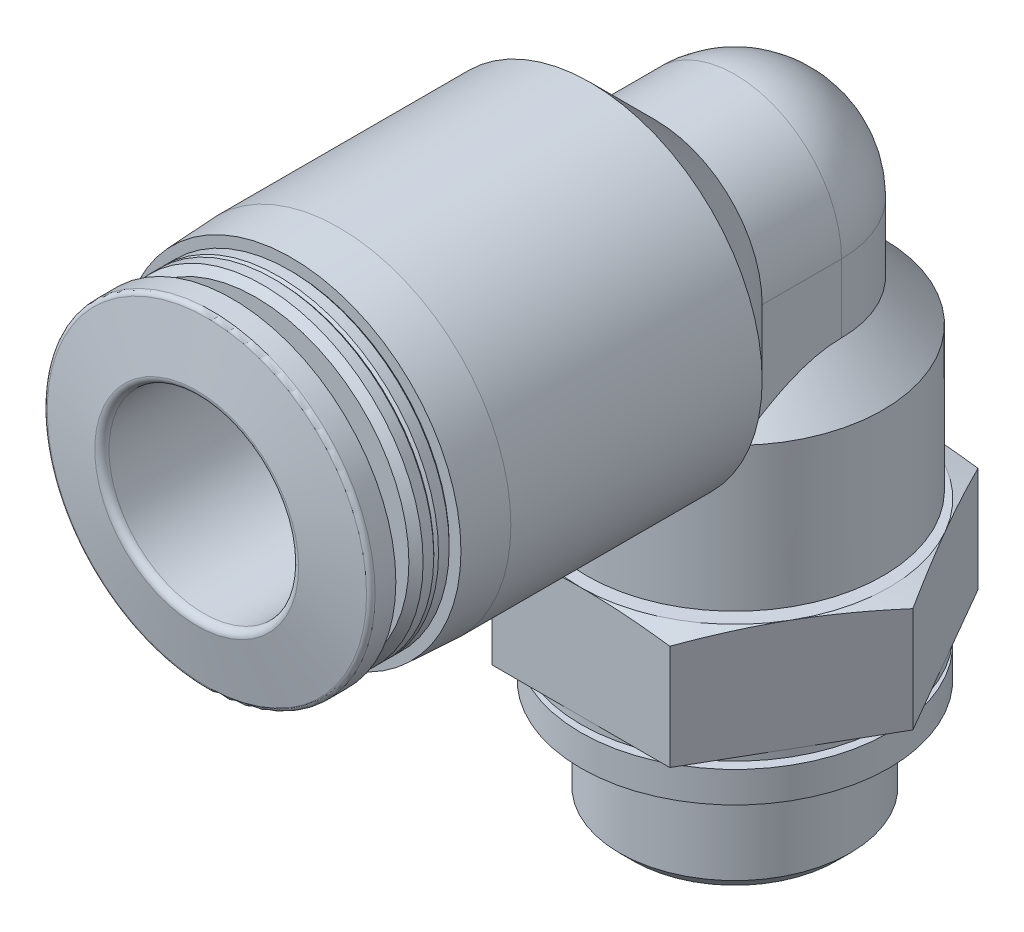
SolidWorks part; units mm, degrees
note: '?' marks a value the reader was unsure of.
ref_plane "Ebene vorne" through (0, 0, 0) normal (0, 0, 1) x (1, 0, 0)
ref_plane "Ebene oben" through (0, 0, 0) normal (0, 1, 0) x (1, 0, 0)
ref_plane "Ebene rechts" through (0, 0, 0) normal (1, 0, 0) x (0, 0, -1)
sketch "Skizze1" plane through (0, 0, 0) normal (0, 0, 1) x (1, 0, 0)
  line L0 (4.495, 17.9) -> (4.495, 15.015)
  line L1 (4.495, 15.015) -> (6.25, 13.26)
  line L2 (6.25, 13.26) -> (6.25, 7.2)
  line L3 (6.25, 7.2) -> (5.625, 6.9)
  line L4 (5.625, 6.9) -> (6.5, 6.9)
  line L5 (6.5, 6.9) -> (7.8, 6.5517)
  line L6 (7.8, 6.5517) -> (7.8, 2.2)
  line L7 (7.8, 2.2) -> (6.5, 2.2)
  line L8 (6.5, 2.2) -> (6.5, 1.9)
  line L9 (6.5, 1.9) -> (6, 1.9)
  line L10 (6, 1.9) -> (6, 1.6)
  line L11 (6, 1.6) -> (6.5, 1.6)
  line L12 (6.5, 1.6) -> (6.5, 0.3)
  line L13 (6.5, 0.3) -> (6, 0.3)
  line L14 (6, 0.3) -> (6, 0)
  line L15 (6, 0) -> (0, 0)
  line L16 (0, 0) -> (0, 22.395)
  line L17 (0, 0) -> (0, 22.395) construction
  arc A0 (0, 22.395) -> (4.495, 17.9) centre (0, 17.9) cw
revolve "Rotation1" add sketch "Skizze1" angle 360 about L17
ref_plane "Ebene1" through (0, 2.2, 0) normal (0, 1, 0) x (1, 0, 0)
sketch "Skizze2" plane through (0, 2.2, 0) normal (0, 1, 0) x (1, 0, 0)
  line L0 (-13, -13) -> (13, -13)
  line L1 (13, -13) -> (13, 13)
  line L2 (13, 13) -> (-13, 13)
  line L3 (-13, 13) -> (-13, -13)
  line L4 (-7.5056, 0) -> (-3.7528, -6.5)
  line L5 (-3.7528, -6.5) -> (3.7528, -6.5)
  line L6 (3.7528, -6.5) -> (7.5056, 0)
  line L7 (7.5056, 0) -> (3.7528, 6.5)
  line L8 (3.7528, 6.5) -> (-3.7528, 6.5)
  line L9 (-3.7528, 6.5) -> (-7.5056, 0)
extrude "Schnitt-Linear austragen1" cut sketch "Skizze2" along normal blind 4.7
sketch "Skizze3" plane through (0, 0, 0) normal (0, 0, 1) x (1, 0, 0)
  line L0 (0, 0) -> (4.864, 0)
  line L1 (4.864, 0) -> (4.864, -3.619)
  line L2 (4.864, -3.619) -> (4.283, -4.2)
  line L3 (4.283, -4.2) -> (0, -4.2)
  line L4 (0, -4.2) -> (0, 0)
  line L5 (0, -4.2) -> (0, 0) construction
revolve "Rotation2" add sketch "Skizze3" angle 360 about L5
cosmetic thread "Gewindedarstellung1" parameters "D1"=4.2, "D2"=8.566
sketch "Skizze4" plane through (0, 0, 0) normal (1, 0, 0) x (0, 0, -1)
  line L0 (-22.7, 17.9) -> (-22.7, 22.2)
  line L1 (-22.7, 22.2) -> (-22.2707, 24.6347)
  line L2 (-22.0737, 24.8) -> (-21.2, 24.8)
  line L3 (-21.2, 24.8) -> (-21.2, 22.95)
  line L4 (-20.9, 22.65) -> (-20.2, 22.65)
  line L5 (-20.2, 22.65) -> (-20.2, 24.35)
  line L6 (-20.2, 24.35) -> (-19.9, 24.65)
  line L7 (-19.9, 24.65) -> (-19.45, 24.65)
  line L8 (-19.45, 24.65) -> (-19.35, 24.55)
  line L9 (-19.35, 24.55) -> (-19.25, 24.65)
  line L10 (-19.25, 24.65) -> (-18.8, 24.65)
  line L11 (-18.8, 24.65) -> (-18.7, 24.55)
  line L12 (-18.7, 24.55) -> (-18.7, 25.0452)
  line L13 (-18.7, 25.0452) -> (-16.7, 25.15)
  line L14 (-16.7, 25.15) -> (-6.1, 25.15)
  line L15 (-6.1, 25.15) -> (-3.345, 22.395)
  line L16 (-3.345, 22.395) -> (0, 22.395)
  line L17 (0, 22.395) -> (0, 17.9)
  line L18 (0, 17.9) -> (-22.7, 17.9)
  line L19 (0, 17.9) -> (-22.7, 17.9) construction
  arc A0 (-22.2707, 24.6347) -> (-22.0737, 24.8) centre (-22.0737, 24.6) cw
  arc A1 (-21.2, 22.95) -> (-20.9, 22.65) centre (-20.9, 22.95) ccw
revolve "Rotation3" add sketch "Skizze4" angle 360 about L19
ref_plane "Ebene2" through (0, 17.9, 0) normal (0, 1, 0) x (1, 0, 0)
sketch "Skizze5" plane through (0, 17.9, 0) normal (0, 1, 0) x (1, 0, 0)
  line L0 (4.495, -4.3425) -> (4.495, 0)
  line L1 (4.495, 0) -> (-4.495, 0)
  line L2 (-4.495, 0) -> (-4.495, -4.3425)
  arc A0 (-4.495, -4.3425) -> (4.495, -4.3425) centre (0, 0) ccw
extrude "Aufsatz-Linear austragen1" add sketch "Skizze5" against normal blind 4.64
ref_plane "Ebene3" through (0, 17.9, 0) normal (0, 1, 0) x (1, 0, 0)
sketch "Skizze6" plane through (0, 0, 0) normal (1, 0, 0) x (0, 0, -1)
  line L0 (-11.325, 14.275) -> (-3.125, 6.075)
  line L1 (-3.125, 6.075) -> (-3.125, 14.275)
  line L2 (-3.125, 14.275) -> (-11.325, 14.275)
extrude "Aufsatz-Linear austragen2" add sketch "Skizze6" against normal blind 1 and the other way blind 1
sketch "Skizze7" plane through (0, 0, 0) normal (0, 0, 1) x (1, 0, 0)
  line L0 (0, 17.9) -> (3, 17.9)
  line L1 (3, 17.9) -> (3, -2.1)
  line L2 (3, -2.1) -> (3.2427, -2.1)
  line L3 (3.2427, -2.1) -> (3.2427, -3.7)
  line L4 (3.2427, -3.7) -> (3.7427, -4.2)
  line L5 (3.7427, -4.2) -> (0, -4.2)
  line L6 (0, -4.2) -> (0, 17.9)
  line L7 (0, -4.2) -> (0, 17.9) construction
revolve "Schnitt-Rotation1" cut sketch "Skizze7" angle 360 about L7
sketch "Skizze8" plane through (0, 0, 0) normal (1, 0, 0) x (0, 0, -1)
  line L0 (-22.7, 17.9) -> (-22.7, 22.2)
  line L1 (-22.4, 21.9) -> (-4.6, 21.9)
  line L2 (-4.6, 21.9) -> (-4.6, 20.9)
  line L3 (-4.6, 20.9) -> (0, 20.9)
  line L4 (3, 17.9) -> (-22.7, 17.9)
  line L5 (0, 17.9) -> (-22.7, 17.9) construction
  arc A0 (-22.7, 22.2) -> (-22.4, 21.9) centre (-22.4, 22.2) ccw
  arc A1 (0, 20.9) -> (3, 17.9) centre (0, 17.9) cw
revolve "Schnitt-Rotation2" cut sketch "Skizze8" angle 360 about L5
ref_plane "Ebene4" through (0, 0, 0) normal (0, 1, 0) x (1, 0, 0)
ref_plane "Ebene5" through (0, 0, 4.6) normal (0, 0, 1) x (1, 0, 0)
ref_plane "ANBAU XY" through (0, 0, 0) normal (0, 1, 0) x (1, 0, 0)
ref_plane "ANBAU XZ" through (0, 0, 0) normal (1, 0, 0) x (0, 0, -1)
ref_plane "ANBAU YZ" through (0, 0, 0) normal (0, 0, -1) x (-1, 0, 0)
ref_axis "ANBAU X" through (0, 0, 50) along (0, 0, -1)?
ref_axis "ANBAU Y" through (80.9, 0, 0) along (-1, 0, 0)?
ref_axis "ANBAU Z" through (0, 50, 0) along (0, -1, 0)?
sketch3d "ANBAU"
  point P0 (0, 0, 0)
ref_plane "ANBAU_FDT3D XY" through (0, 0, 0) normal (0, -1, 0) x (-1, 0, 0)
ref_plane "ANBAU_FDT3D XZ" through (0, 0, 0) normal (0, 0, 1) x (1, 0, 0)
ref_plane "ANBAU_FDT3D YZ" through (0, 0, 0) normal (-1, 0, 0) x (0, 0, 1)
ref_axis "ANBAU_FDT3D X" through (80.9, 0, 0) along (-1, 0, 0)?
ref_axis "ANBAU_FDT3D Y" through (0, 0, 50) along (0, 0, -1)?
ref_axis "ANBAU_FDT3D Z" through (0, -50, 0) along (0, 1, 0)?
sketch3d "ANBAU_FDT3D"
  point P0 (0, 0, 0)
ref_plane "ANBAU_STD XY" through (0, 0, 0) normal (0, 1, 0) x (1, 0, 0)
ref_plane "ANBAU_STD XZ" through (0, 0, 0) normal (-1, 0, 0) x (0, 0, 1)
ref_plane "ANBAU_STD YZ" through (0, 0, 0) normal (0, 0, 1) x (1, 0, 0)
ref_axis "ANBAU_STD X" through (0, 0, -50) along (0, 0, 1)?
ref_axis "ANBAU_STD Y" through (-80.9, 0, 0) along (1, 0, 0)?
ref_axis "ANBAU_STD Z" through (0, 50, 0) along (0, -1, 0)?
sketch3d "ANBAU_STD"
  point P0 (0, 0, 0)
ref_plane "CPV XY" through (0, 0, 0) normal (0, 1, 0) x (1, 0, 0)
ref_plane "CPV XZ" through (0, 0, 0) normal (0, 0, 1) x (1, 0, 0)
ref_plane "CPV YZ" through (0, 0, 0) normal (1, 0, 0) x (0, 0, -1)
ref_axis "CPV X" through (-80.9, 0, 0) along (1, 0, 0)?
ref_axis "CPV Y" through (0, 0, 50) along (0, 0, -1)?
ref_axis "CPV Z" through (0, 50, 0) along (0, -1, 0)?
sketch3d "CPV"
  point P0 (0, 0, 0)
ref_plane "EP_MPAC XY" through (0, 0, 0) normal (0, 1, 0) x (1, 0, 0)
ref_plane "EP_MPAC XZ" through (0, 0, 0) normal (-1, 0, 0) x (0, 0, 1)
ref_plane "EP_MPAC YZ" through (0, 0, 0) normal (0, 0, 1) x (1, 0, 0)
ref_axis "EP_MPAC X" through (0, 0, -50) along (0, 0, 1)?
ref_axis "EP_MPAC Y" through (-80.9, 0, 0) along (1, 0, 0)?
ref_axis "EP_MPAC Z" through (0, 50, 0) along (0, -1, 0)?
sketch3d "EP_MPAC"
  point P0 (0, 0, 0)
ref_plane "FDT_SCHLAUCH XY" through (0, 0, 4.6) normal (0, 0, 1) x (1, 0, 0)
ref_plane "FDT_SCHLAUCH XZ" through (0, 17.9, 0) normal (0, 1, 0) x (1, 0, 0)
ref_plane "FDT_SCHLAUCH YZ" through (0, 0, 0) normal (-1, 0, 0) x (0, 0, 1)
ref_axis "FDT_SCHLAUCH X" through (80.9, 17.9, 4.6) along (-1, 0, 0)?
ref_axis "FDT_SCHLAUCH Y" through (0, 50, 4.6) along (0, -1, 0)?
ref_axis "FDT_SCHLAUCH Z" through (0, 17.9, 80.9) along (0, 0, -1)?
sketch3d "FDT_SCHLAUCH"
  point P0 (0, 17.9, 4.6)
